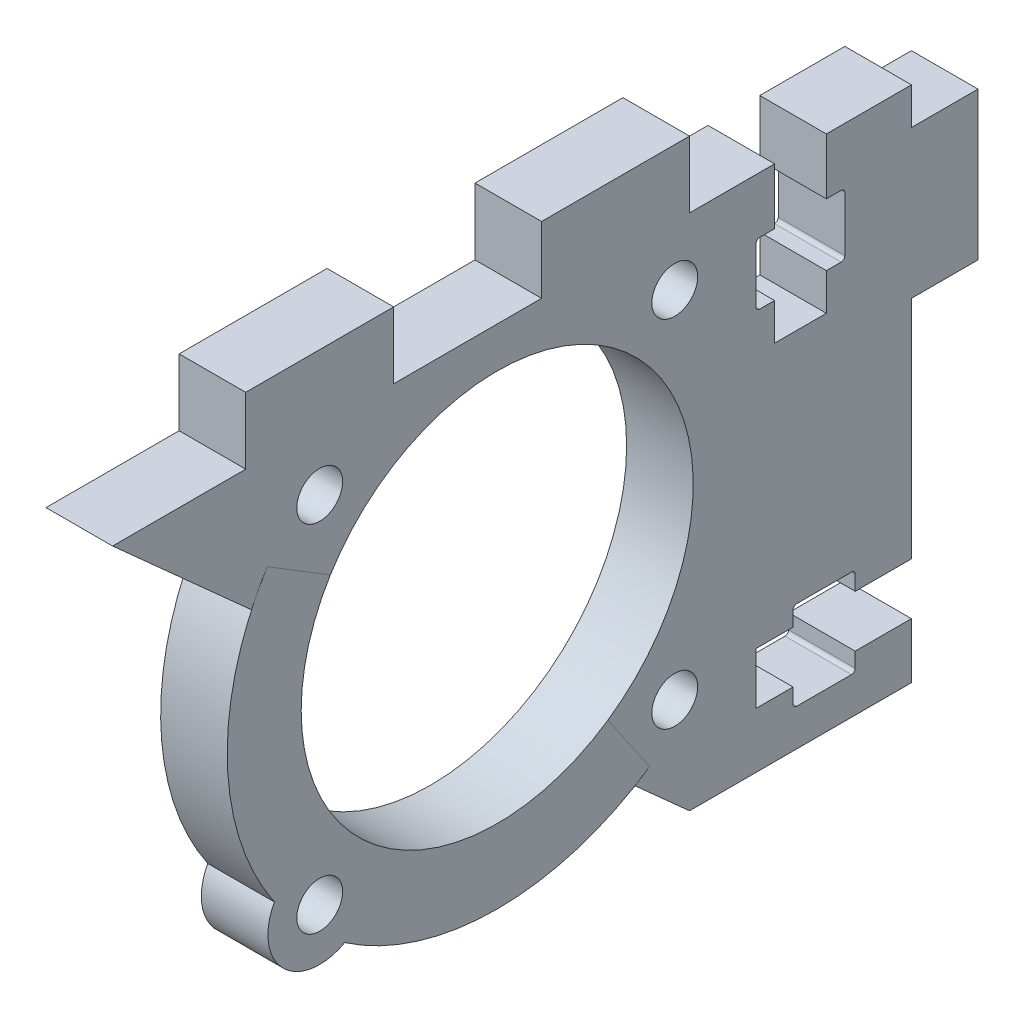
SolidWorks part; units mm, degrees
ref_plane "Front Plane" through (0, 0, 0) normal (0, 0, 1) x (1, 0, 0)
ref_plane "Top Plane" through (0, 0, 0) normal (0, 1, 0) x (1, 0, 0)
ref_plane "Right Plane" through (0, 0, 0) normal (1, 0, 0) x (0, 0, -1)
sketch "Sketch1" plane through (0, 0, 0) normal (1, 0, 0) x (0, 0, -1)
  line L0 (0, 0) -> (0, -35)
  line L1 (0, -35) -> (-54, 0)
  line L2 (-54, 0) -> (0, 0)
  dimension "D1" = 35
  dimension "D2" = 54
extrude "Boss-Extrude1" add sketch "Sketch1" along normal blind 4.5
sketch "Sketch2" plane through (4.5, 0, 0) normal (1, 0, 0) x (0, 0, -1)
  line L0 (0, -35) -> (0, 0) construction
  line L1 (-4.5, -2.5) -> (4.5, -2.5)
  line L2 (-4.5, -2.5) -> (-4.5, -12.5)
  line L3 (-4.5, -12.5) -> (4.5, -12.5)
  line L4 (4.5, -2.5) -> (4.5, -12.5)
  line L5 (-4.5, -2.5) -> (4.5, -12.5) construction
  line L6 (-4.5, -12.5) -> (4.5, -2.5) construction
  line L7 (0, 0) -> (-54, 0) construction
  point P0 (0, -7.5)
  dimension "D1" = 10
  dimension "D2" = 7.5
  dimension "D3" = 4.5
extrude "Boss-Extrude2" add sketch "Sketch2" against normal through all
sketch "Sketch3" plane through (4.5, 0, 0) normal (1, 0, 0) x (0, 0, -1)
  line L0 (0, -35) -> (-15, -35)
  line L1 (0, -25) -> (-54, 0)
  line L4 (0, -35) -> (0, -12.5) construction
  line L5 (0, -25) -> (0, -35)
  line L6 (-54, 0) -> (-15, -35)
  dimension "D1" = 15
  dimension "D2" = 10
extrude "Boss-Extrude3" add sketch "Sketch3" against normal through all
sketch "Sketch4" plane through (4.5, 0, 0) normal (1, 0, 0) x (0, 0, -1)
  line L0 (0, -29.5) -> (-10.5, -29.5) construction
  line L1 (0, -35) -> (0, -12.5) construction
  line L2 (0, -27.75) -> (-10.5, -27.75) construction
  line L3 (-10.5, -27.75) -> (-10.5, -31.25) construction
  line L4 (0, -31.25) -> (0, -27.75)
  line L5 (0, -27.75) -> (-3.8, -27.75)
  line L6 (-3.8, -27.75) -> (-3.8, -26.75)
  line L7 (-4.05, -26.5) -> (-7.75, -26.5)
  line L8 (-8, -26.75) -> (-8, -27.75)
  line L9 (-8, -27.75) -> (-10.5, -27.75)
  line L10 (-10.5, -27.75) -> (-10.5, -31.25)
  line L12 (0, -31.25) -> (-10.5, -31.25) construction
  line L13 (-8, -31.25) -> (-10.5, -31.25)
  line L14 (-8, -32.25) -> (-8, -31.25)
  line L15 (-4.05, -32.5) -> (-7.75, -32.5)
  line L16 (-3.8, -31.25) -> (-3.8, -32.25)
  line L17 (0, -31.25) -> (-3.8, -31.25)
  line L18 (4.5, -12.5) -> (4.5, -2.5) construction
  line L19 (0, -18.5) -> (-33.3857, -18.5) construction
  line L20 (-54, 0) -> (-15, -35) construction
  line L37 (0, -31.25) -> (-10.5, -31.25) construction
  arc A0 (-8, -32.25) -> (-7.75, -32.5) centre (-7.75, -32.25) ccw
  arc A1 (-4.05, -32.5) -> (-3.8, -32.25) centre (-4.05, -32.25) ccw
  arc A2 (-3.8, -26.75) -> (-4.05, -26.5) centre (-4.05, -26.75) ccw
  arc A3 (-7.75, -26.5) -> (-8, -26.75) centre (-7.75, -26.75) ccw
  point P10 (4.5, -7.5)
  point P20 (-8, -32.5)
  point P23 (-3.8, -32.5)
  point P26 (-3.8, -26.5)
  point P29 (-8, -26.5)
  dimension "D7" = 0.25
  dimension "D1" = 10.5
  dimension "D2" = 1.75
  dimension "D3" = 3
  dimension "D4" = 4.2
  dimension "D5" = 8
  dimension "D6" = 22
extrude "Cut-Extrude1" cut sketch "Sketch4" against normal through all
sketch "Sketch5" plane through (4.5, 0, 0) normal (1, 0, 0) x (0, 0, -1)
  line L0 (0, 0) -> (-54, 0) construction
  line L1 (-25, 4.5) -> (-15, 4.5)
  line L2 (-25, 4.5) -> (-25, 0)
  line L3 (0, 0) -> (-54, 0) construction
  line L4 (-15, 4.5) -> (-15, 0)
  line L5 (-25, 4.5) -> (-20, 0) construction
  line L6 (-20, 0) -> (-15, 4.5) construction
  line L7 (-30, 0) -> (-30, 4.5) construction
  line L8 (-40, 0) -> (-45, 4.5) construction
  line L9 (-35, 4.5) -> (-40, 0) construction
  line L10 (-45, 4.5) -> (-45, 0)
  line L12 (-35, 4.5) -> (-35, 0)
  line L13 (-35, 4.5) -> (-45, 4.5)
  line L14 (-20, 0) -> (-15, 4.5) construction
  line L15 (-15, 0) -> (-25, 0)
  line L16 (-35, 0) -> (-45, 0)
  point P0 (-20, 0)
  point P14 (-40, 0)
  dimension "D3" = 4.5
  dimension "D1" = 20
  dimension "D2" = 10
  dimension "D4" = 20
  dimension "D5" = 5
extrude "Boss-Extrude4" add sketch "Sketch5" against normal through all
sketch "Sketch8" [suppressed] plane through (4.5, 0, 0) normal (1, 0, 0) x (0, 0, -1)
  line L0 (-15, -30) -> (-27, -30) construction
  line L1 (-15, -35) -> (-27, -35)
  line L2 (-15, -25) -> (-27, -25)
  line L3 (-15, -35) -> (0, -35) construction
  line L4 (-15, -25) -> (-15, -35)
  arc A1 (-27, -25) -> (-27, -35) centre (-27, -30) ccw
  dimension "D5" = 5
  dimension "D1" = 0
  dimension "D2" = 12
  dimension "D3" = 0
  dimension "D4" = 10
extrude "Boss-Extrude5" [suppressed] add sketch "Sketch8" against normal up to surface (4.5 mm away) up to face at (0, -17.3125, 11.7125)
sketch "Sketch9" [suppressed] plane through (4.5, 0, 0) normal (1, 0, 0) x (0, 0, -1)
  line L0 (-27, -30) -> (-22, -30) construction
  line L1 (-27, -27) -> (-22, -27)
  line L2 (-27, -33) -> (-22, -33)
  arc A0 (-27, -27) -> (-27, -33) centre (-27, -30) ccw
  arc A1 (-22, -33) -> (-22, -27) centre (-22, -30) ccw
  point P3 (-24.5, -30)
  dimension "D1" = 3
  dimension "D2" = 5
extrude "Cut-Extrude3" [suppressed] cut sketch "Sketch9" against normal through all
sketch "Sketch10" plane through (0, 0, 0) normal (-1, 0, 0) x (0, 0, 1)
  line L0 (15, -35) -> (54, -12)
  line L1 (54, -12) -> (54, 0)
  line L3 (54, 0) -> (15, -35)
  dimension "D1" = 12
extrude "Boss-Extrude6" [suppressed] add sketch "Sketch10" against normal through all
sketch "Sketch6" plane through (4.5, 0, 0) normal (1, 0, 0) x (0, 0, -1)
  line L0 (-30, 0) -> (-30, -10.5) construction
  line L1 (-25, 0) -> (-35, 0) construction
  line L2 (-28.25, -10.5) -> (-31.75, -10.5) construction
  line L3 (-31.75, -10.5) -> (-31.75, 0) construction
  line L4 (-28.25, 0) -> (-31.75, 0)
  line L5 (-31.75, 0) -> (-31.75, -3.8)
  line L6 (-31.75, -3.8) -> (-32.75, -3.8)
  line L7 (-33, -4.05) -> (-33, -7.75)
  line L8 (-32.75, -8) -> (-31.75, -8)
  line L9 (-31.75, -8) -> (-31.75, -10.5)
  line L10 (-31.75, -10.5) -> (-28.25, -10.5)
  line L11 (-28.25, -10.5) -> (-28.25, 0) construction
  line L12 (-28.25, -8) -> (-28.25, -10.5)
  line L13 (-27.25, -8) -> (-28.25, -8)
  line L14 (-27, -4.05) -> (-27, -7.75)
  line L15 (-28.25, -3.8) -> (-27.25, -3.8)
  line L16 (-28.25, 0) -> (-28.25, -3.8)
  arc A0 (-33, -7.75) -> (-32.75, -8) centre (-32.75, -7.75) ccw
  arc A1 (-32.75, -3.8) -> (-33, -4.05) centre (-32.75, -4.05) ccw
  arc A2 (-27.25, -3.8) -> (-27, -4.05) centre (-27.25, -4.05) cw
  arc A3 (-27, -7.75) -> (-27.25, -8) centre (-27.25, -7.75) cw
  point P12 (-33, -8)
  point P15 (-33, -3.8)
  point P26 (-27, -3.8)
  point P27 (-27, -8)
  dimension "D1" = 10.5
  dimension "D2" = 1.75
  dimension "D4" = 4.2
  dimension "D6" = 0.25
  dimension "D3" = 8
  dimension "D5" = 3
extrude "Cut-Extrude2" [suppressed] cut sketch "Sketch6" against normal through all
sketch "Sketch11" plane through (0, 0, 0) normal (-1, 0, 0) x (0, 0, 1)
  line L0 (7.5, 0) -> (7.5, -10.5) construction
  line L1 (0, 0) -> (15, 0) construction
  line L2 (5.75, -10.5) -> (9.25, -10.5)
  line L3 (9.25, -10.5) -> (9.25, -8)
  line L4 (9.25, -8) -> (10.25, -8)
  line L5 (10.5, -7.75) -> (10.5, -4.05)
  line L6 (10.25, -3.8) -> (9.25, -3.8)
  line L7 (9.25, -3.8) -> (9.25, 0)
  line L8 (9.25, 0) -> (5.75, 0)
  line L9 (9.25, -8) -> (9.25, -3.8) construction
  line L10 (0, 0) -> (15, 0) construction
  line L11 (5.75, -8) -> (5.75, -3.8) construction
  line L12 (5.75, -3.8) -> (5.75, 0)
  line L13 (4.75, -3.8) -> (5.75, -3.8)
  line L14 (4.5, -7.75) -> (4.5, -4.05)
  line L15 (5.75, -8) -> (4.75, -8)
  line L16 (5.75, -10.5) -> (5.75, -8)
  arc A0 (10.5, -4.05) -> (10.25, -3.8) centre (10.25, -4.05) ccw
  arc A1 (4.75, -3.8) -> (4.5, -4.05) centre (4.75, -4.05) ccw
  arc A2 (10.25, -8) -> (10.5, -7.75) centre (10.25, -7.75) ccw
  arc A3 (4.5, -7.75) -> (4.75, -8) centre (4.75, -7.75) ccw
  point P11 (7.5, 0)
  point P22 (10.5, -3.8)
  point P25 (4.5, -3.8)
  point P28 (10.5, -8)
  point P31 (4.5, -8)
  dimension "D7" = 0.25
  dimension "D1" = 10.5
  dimension "D3" = 3
  dimension "D8" = 0.25
  dimension "D2" = 4.2
  dimension "D4" = 8
  dimension "D5" = 1.75
  dimension "D6" = 0
extrude "Cut-Extrude4" cut sketch "Sketch11" against normal through all
sketch "Sketch12" plane through (0, 0, 0) normal (-1, 0, 0) x (0, 0, 1)
  line L0 (28, -16) -> (16, -4) construction
  line L1 (28, -16) -> (28, -2.75) construction
  line L2 (28, -16) -> (40, -4) construction
  line L3 (28, -16) -> (14.75, -16) construction
  line L4 (28, -16) -> (16, -28) construction
  line L5 (28, -16) -> (16, -4) construction
  line L6 (0, -27.75) -> (0, -12.5) construction
  line L7 (25, 0) -> (35, 0) construction
  circle A0 centre (28, -16) radius 13.25
  circle A1 centre (16, -4) radius 1.55
  circle A2 centre (40, -4) radius 1.55
  circle A3 centre (16, -28) radius 1.55
  dimension "D1" = 26.5
  dimension "D2" = 3.1
  dimension "D3" = 12
  dimension "D4" = 45
  dimension "D5" = 28
  dimension "D6" = 16
extrude "Cut-Extrude5" cut sketch "Sketch12" against normal through all
sketch "Sketch13" plane through (0, 0, 0) normal (-1, 0, 0) x (0, 0, 1)
  line L0 (39.2845, -9.0557) -> (43.5428, -6.4352)
  line L1 (20.5179, -26.9353) -> (17.6945, -31.0619)
  line L6 (28, -16) -> (54, 0) construction
  line L7 (28, -16) -> (15, -35) construction
  arc A0 (20.5179, -26.9353) -> (39.2845, -9.0557) centre (28, -16) ccw
  arc A1 (17.6945, -31.0619) -> (43.5428, -6.4352) centre (28, -16) ccw
  arc A3 (40.6311, -11.9977) -> (22.6595, -28.1261) centre (28, -16) ccw construction
  dimension "D1" = 5
extrude "Boss-Extrude7" add sketch "Sketch13" against normal through all
sketch "Sketch14" plane through (0, 0, 0) normal (-1, 0, 0) x (0, 0, 1)
  line L0 (28, -2.75) -> (28, -29.25) construction
  line L1 (28, -16) -> (40, -28) construction
  circle A0 centre (28, -16) radius 13.25 construction
  circle A1 centre (40, -28) radius 3.5
  dimension "D2" = 7
  dimension "D1" = 45
  dimension "D3" = 12
extrude "Boss-Extrude8" add sketch "Sketch14" against normal through all
sketch "Sketch15" plane through (0, 0, 0) normal (-1, 0, 0) x (0, 0, 1)
  line L0 (42.4749, -30.4749) -> (28, -16) construction
  arc A0 (38.305, -31.0622) -> (43.0622, -26.305) centre (40, -28) ccw construction
  circle A1 centre (40, -28) radius 1.55
  dimension "D1" = 3.1
extrude "Cut-Extrude6" cut sketch "Sketch15" against normal through all
sketch "Sketch16" [suppressed] plane through (4.5, 0, 0) normal (1, 0, 0) x (0, 0, -1)
  line L0 (0, -25) -> (-39, -25) construction
  line L1 (0, -27.75) -> (0, -12.5) construction
  line L2 (-20, -25) -> (-39, -25) construction
  line L3 (-20, -29) -> (-39, -29)
  line L4 (-20, -21) -> (-39, -21)
  line L5 (-15, -35) -> (0, -35) construction
  arc A0 (-20, -29) -> (-20, -21) centre (-20, -25) ccw
  arc A1 (-39, -21) -> (-39, -29) centre (-39, -25) ccw
  point P5 (-29.5, -25)
  point P12 (0, -20.125)
  dimension "D1" = 4
  dimension "D2" = 10
  dimension "D3" = 39
  dimension "D4" = 20
extrude "Boss-Extrude9" [suppressed] add sketch "Sketch16" against normal through all
sketch "Sketch17" [suppressed] plane through (4.5, 0, 0) normal (1, 0, 0) x (0, 0, -1)
  line L0 (-43, -25) -> (0, -25) construction
  line L1 (0, -27.75) -> (0, -12.5) construction
  line L2 (-26.5, -25) -> (-26.5, -20.0064) construction
  arc A0 (-39, -21) -> (-39, -29) centre (-39, -25) ccw construction
  circle A1 centre (-39, -25) radius 1.55
  circle A2 centre (-14, -25) radius 1.55
  dimension "D1" = 3.1
  dimension "D2" = 12.5
extrude "Cut-Extrude7" [suppressed] cut sketch "Sketch17" against normal through all
equation "\"X-ROD-SPACING\"=45"
equation "\"Y-ROD-SPACING\"=75"
equation "\"Z-ROD-SPACING\"=17.5"
equation "\"Y-BED-OFFSET\"=2"
equation "\"Y-BED-ROD-INSET\"=3.5"
equation "\"Y-BED-SCREW-SPACING\"=209"
equation "\"Y-BED-SCREW-CUTOUT-SLOT-HEIGHT\"=2"
equation "\"T-SLOT-NUT-FILLET-RADIUS\"=0.25"
equation "\"T-SLOT-SCREW-SHAFT-RADIUS\"=1.75"
equation "\"T-SLOT-SCREW-SHAFT-CUTOUT-LENGTH\"=10.5"
equation "\"T-SLOT-NUT-DEPTH\"=4.2"
equation "\"T-SLOT-NUT-WIDTH\"=3"
equation "\"T-SLOT-NUT-END-DISTANCE\"=8"
equation "\"ACRYLIC-THICKNESS\"=10"
equation "\"ACRYLIC-THICKNESS2\"=4.5"
equation "\"ACRYLIC-TAB-CUTOUT-SIZE\"=\"ACRYLIC-THICKNESS\"+\"ACRYLIC-TAB-TOLERANCE\"*2"
equation "\"ACRYLIC-TAB-WIDTH\"=\"ACRYLIC-THICKNESS\""
equation "\"ACRYLIC-M3-HOLE\"=3.1"
equation "\"SMOOTHROD-CAP-SCREW-DISTANCE\"=20"
equation "\"FRAME-WIDTH-INNER\"=370"
equation "\"NEMA17-HOLE-SPACING\"=31"
equation "\"NEMA17-CENTRAL-CUTOUT\"=22.5"
equation "\"Z-BRACKET-REACH\"=55"
equation "\"Z-ROD-INSET\"=16"
equation "\"TOP-BRACKET-SPACING\"=40"
equation "\"SMOOTHROD-X-LENGTH\"=350"
equation "\"SMOOTHROD-Y-LENGTH\"=350"
equation "\"SMOOTHROD-Z-LENGTH\"=350"
equation "\"SMOOTHROD-TIGHTENING-HEADROOM\"=.25"
equation "\"LEADSCREW-Z-LENGTH\"=300"
equation "\"SCREW-LENGTH-FRAME\"=\"ACRYLIC-THICKNESS\" + 10"
equation "\"SCREW-LENGTH-MOTOR\"=\"ACRYLIC-THICKNESS\" + 5"
equation "\"SCREW-LENGTH-EXTRUDER\"=28"
equation "\"SCREW-HEAD-RADIUS\"=6"
equation "\"PRINTED-X-SMOOTHROD-DIAMETER\"=8.2"
equation "\"PRINTED-X-SMOOTHROD-CUTOUT\"=10"
equation "\"PRINTED-X-BASE-HEIGHT\"=10"
equation "\"PRINTED-LM8UU-CUTOUT-SIZE\"=15.25"
equation "\"PRINTED-LM8UU-CUTOUT-LENGTH\"=24.5"
equation "\"PRINTED-X-IDLER-HEIGHT\"=16"
equation "\"PSU-MOUNTING-WIDTH\"=95"
equation "\"PSU-MOUNTING-HEIGHT\"=177"
equation "\"Y-BELT-TO-ROD-DISTANCE\"=20"
equation "\"SPOOL-HOLDER-ROD-SPACING\"=150"
equation "\"ACRYLIC-X-CARRIAGE-WIDTH\"=55"
equation "\"ACRYLIC-X-CARRIAGE-HEIGHT\"=75"
equation "\"ACRYLIC-X-CARRIAGE-SCREW-SPACING-X\"=15"
equation "\"ACRYLIC-X-CARRIAGE-SCREW-SPACING-Y\"=33"
equation "\"ACRYLIC-X-CARRIAGE-CENTER-TAB-SPACING\"=14"
equation "\"ACRYLIC-X-CARRIAGE-EXTRUDER-SHELF-DEPTH\"=\"ACRYLIC-X-CARRIAGE-EXTRUDER-OFFSET\" + 28"
equation "\"D2@Sketch1\"=\"ACRYLIC-X-CARRIAGE-EXTRUDER-SHELF-DEPTH\""
equation "\"D1@Boss-Extrude1\"=\"ACRYLIC-THICKNESS2\""
equation "\"D1@Sketch2\"=\"ACRYLIC-TAB-WIDTH\""
equation "\"D3@Sketch2\"=\"ACRYLIC-THICKNESS2\""
equation "\"ACRYLIC-X-CARRIAGE-LM8UU-CUTOUT-WIDTH\"=24.25"
equation "\"ACRYLIC-X-CARRIAGE-EXTRUDER-BRACE-SPACING\"=23"
equation "\"ACRYLIC-X-CARRIAGE-EXTRUDER-BRACE-HEIGHT\"=35"
equation "\"D1@Sketch1\"=\"ACRYLIC-X-CARRIAGE-EXTRUDER-BRACE-HEIGHT\""
equation "\"D1@Sketch4\"=\"T-SLOT-SCREW-SHAFT-CUTOUT-LENGTH\""
equation "\"D2@Sketch4\"=\"T-SLOT-SCREW-SHAFT-RADIUS\""
equation "\"D3@Sketch4\"=\"T-SLOT-NUT-WIDTH\""
equation "\"D4@Sketch4\"=\"T-SLOT-NUT-DEPTH\""
equation "\"D5@Sketch4\"=\"T-SLOT-NUT-END-DISTANCE\""
equation "\"D7@Sketch4\"=\"T-SLOT-NUT-FILLET-RADIUS\""
equation "\"ACRYLIC-X-CARRIAGE-EXTRUDER-BRACE-SCREW-SPACING\"=22"
equation "\"D6@Sketch4\"=\"ACRYLIC-X-CARRIAGE-EXTRUDER-BRACE-SCREW-SPACING\""
equation "\"ACRYLIC-X-CARRIAGE-EXTRUDER-BRACE-TAB-OFFSET\"=20"
equation "\"D1@Sketch5\"=\"ACRYLIC-X-CARRIAGE-EXTRUDER-BRACE-TAB-OFFSET\""
equation "\"D2@Sketch5\"=\"ACRYLIC-TAB-WIDTH\""
equation "\"D3@Sketch5\"=\"ACRYLIC-THICKNESS2\""
equation "\"ACRYLIC-X-CARRIAGE-EXTRUDER-OFFSET\"=26"
equation "\"ACRYLIC-X-CARRIAGE-EXTRUDER-ANGLE\"=90"
equation "\"D1@Sketch6\"=\"T-SLOT-SCREW-SHAFT-CUTOUT-LENGTH\""
equation "\"D2@Sketch6\"=\"T-SLOT-SCREW-SHAFT-RADIUS\""
equation "\"D3@Sketch6\"=\"T-SLOT-NUT-END-DISTANCE\""
equation "\"D4@Sketch6\"=\"T-SLOT-NUT-DEPTH\""
equation "\"D5@Sketch6\"=\"T-SLOT-NUT-WIDTH\""
equation "\"D6@Sketch6\"=\"T-SLOT-NUT-FILLET-RADIUS\""
equation "\"D1@Sketch11\"=\"T-SLOT-SCREW-SHAFT-CUTOUT-LENGTH\""
equation "\"D2@Sketch11\"=\"T-SLOT-NUT-DEPTH\""
equation "\"D3@Sketch11\"=\"T-SLOT-NUT-WIDTH\""
equation "\"D4@Sketch11\"=\"T-SLOT-NUT-END-DISTANCE\""
equation "\"D5@Sketch11\"=\"T-SLOT-SCREW-SHAFT-RADIUS\""
equation "\"D7@Sketch11\"=\"T-SLOT-NUT-FILLET-RADIUS\""
equation "\"D8@Sketch11\"=\"T-SLOT-NUT-FILLET-RADIUS\""
equation "\"D2@Sketch12\"=\"ACRYLIC-M3-HOLE\""
equation "\"D1@Sketch15\"=\"ACRYLIC-M3-HOLE\""
equation "\"D1@Sketch17\"=\"ACRYLIC-M3-HOLE\""
